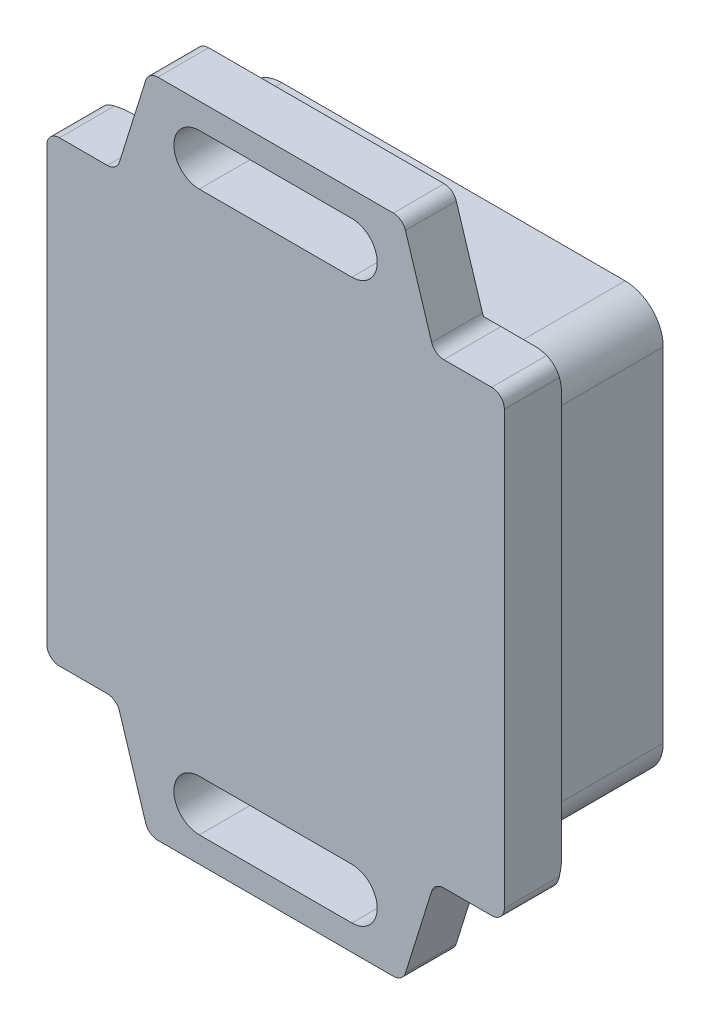
SolidWorks part; units mm, degrees
ref_plane "Plan de face" through (0, 0, 0) normal (0, 0, 1) x (1, 0, 0)
ref_plane "Plan de dessus" through (0, 0, 0) normal (0, 1, 0) x (1, 0, 0)
ref_plane "Plan de droite" through (0, 0, 0) normal (1, 0, 0) x (0, 0, -1)
sketch "Esquisse1" plane through (0, 0, 0) normal (0, 0, 1) x (1, 0, 0)
  line L1 (10.5, 10.5) -> (-10.5, 10.5)
  line L2 (10.5, 10.5) -> (10.5, -10.5)
  line L3 (10.5, -10.5) -> (-10.5, -10.5)
  line L4 (-10.5, 10.5) -> (-10.5, -10.5)
  line L5 (10.5, 10.5) -> (-10.5, -10.5) construction
  line L6 (10.5, -10.5) -> (-10.5, 10.5) construction
  line L7 (16.5, 16.5) -> (-16.5, 16.5)
  line L8 (16.5, 16.5) -> (16.5, -16.5)
  line L9 (16.5, -16.5) -> (-16.5, -16.5)
  line L10 (-16.5, 16.5) -> (-16.5, -16.5)
  line L11 (16.5, 16.5) -> (-16.5, -16.5) construction
  line L12 (16.5, -16.5) -> (-16.5, 16.5) construction
  point P0 (0, 0)
  point P6 (0, 0)
  dimension "D1" = 21
  dimension "D2" = 6
  dimension "D3" = 6
extrude "Boss.-Extru.1" add sketch "Esquisse1" along normal blind 10
sketch "Esquisse2" plane through (0, 0, 10) normal (0, 0, 1) x (1, 0, 0)
  line L2 (18, 18) -> (-18, 18)
  line L3 (18, 18) -> (18, -18)
  line L4 (18, -18) -> (-18, -18)
  line L5 (-10.5, 10.5) -> (-10.5, -10.5)
  line L6 (10.5, 10.5) -> (-10.5, 10.5)
  line L7 (10.5, -10.5) -> (10.5, 10.5)
  line L8 (-10.5, -10.5) -> (10.5, -10.5)
  line L9 (-10.5, 10.5) -> (-10.5, -10.5)
  line L10 (10.5, 10.5) -> (-10.5, 10.5)
  line L11 (10.5, -10.5) -> (10.5, 10.5)
  line L12 (-10.5, -10.5) -> (10.5, -10.5)
  line L13 (-18, 18) -> (-18, -18)
  line L14 (18, 18) -> (-18, -18) construction
  line L15 (18, -18) -> (-18, 18) construction
  point P0 (0, 0)
  dimension "D2" = 36
  dimension "D3" = 36
  dimension "D1" = 0
extrude "Boss.-Extru.2" add sketch "Esquisse2" along normal blind 4
sketch "Esquisse3" plane through (0, 0, 14) normal (0, 0, 1) x (1, 0, 0)
  line L0 (0, 0) -> (18, 0) construction
  line L1 (18, -18) -> (18, 18) construction
  line L2 (0, 18) -> (0, 0) construction
  line L3 (18, 18) -> (-18, 18) construction
  line L4 (12.5, 18) -> (-12.5, 18)
  line L5 (-12.5, 18) -> (-10, 26)
  line L6 (-10, 26) -> (10, 26)
  line L7 (0, 18) -> (0, 26) construction
  line L8 (12.5, 18) -> (10, 26)
  line L9 (0, -18) -> (0, -26) construction
  line L10 (12.5, -18) -> (10, -26)
  line L11 (-10, -26) -> (10, -26)
  line L12 (-12.5, -18) -> (-10, -26)
  line L13 (12.5, -18) -> (-12.5, -18)
  line L14 (-6, 22) -> (6, 22) construction
  line L15 (-6, 24) -> (6, 24)
  line L16 (-6, 20) -> (6, 20)
  line L17 (-6, -22) -> (6, -22) construction
  line L18 (-6, -24) -> (6, -24)
  line L19 (-6, -20) -> (6, -20)
  arc A0 (-6, 24) -> (-6, 20) centre (-6, 22) ccw
  arc A1 (6, 20) -> (6, 24) centre (6, 22) ccw
  arc A2 (-6, -24) -> (-6, -20) centre (-6, -22) cw
  arc A3 (6, -20) -> (6, -24) centre (6, -22) cw
  point P21 (0, 22)
  point P28 (0, -22)
  dimension "D1" = 8
  dimension "D2" = 25
  dimension "D3" = 20
  dimension "D4" = 4
  dimension "D5" = 12
extrude "Boss.-Extru.3" add sketch "Esquisse3" against normal blind 4
chamfer "Chanfrein1" distance 2 angle 45 4 edges at (0, -16.5, 10) (16.5, 0, 10) (0, 16.5, 10) (-16.5, 0, 10)
fillet "Congé1" radius 1 16 edges at (18, -18, 11.75) (12.5, -18, 11.75) (10, -26, 12) (-10, -26, 12) (-12.5, -18, 11.75) (-18, -18, 11.75) (-12.5, 18, 11.75) (-18, 18, 11.75) (18, 18, 11.75) (12.5, 18, 11.75) (-10, 26, 12) (10, 26, 12) (10.5, -10.5, 7) (10.5, 10.5, 7) (-10.5, 10.5, 7) (-10.5, -10.5, 7)
fillet "Congé2" radius 3 8 edges at (17.1036, -17.1036, 8.6036) (-17.1036, -17.1036, 8.6036) (-17.1036, 17.1036, 8.6036) (17.1036, 17.1036, 8.6036) (16.5, 16.5, 4) (16.5, -16.5, 4) (-16.5, 16.5, 4) (-16.5, -16.5, 4)
sketch "Esquisse4" plane through (0, 0, 14) normal (0, 0, 1) x (1, 0, 0)
  line L5 (-9.5, -10.5) -> (9.5, -10.5)
  line L6 (-10.5, 9.5) -> (-10.5, -9.5)
  line L7 (9.5, 10.5) -> (-9.5, 10.5)
  line L8 (10.5, -9.5) -> (10.5, 9.5)
  line L9 (-9.5, -10.5) -> (9.5, -10.5)
  line L10 (-10.5, 9.5) -> (-10.5, -9.5)
  line L11 (9.5, 10.5) -> (-9.5, 10.5)
  line L12 (10.5, -9.5) -> (10.5, 9.5)
  arc A4 (-10.5, -9.5) -> (-9.5, -10.5) centre (-9.5, -9.5) ccw
  arc A5 (-9.5, 10.5) -> (-10.5, 9.5) centre (-9.5, 9.5) ccw
  arc A6 (10.5, 9.5) -> (9.5, 10.5) centre (9.5, 9.5) ccw
  arc A7 (9.5, -10.5) -> (10.5, -9.5) centre (9.5, -9.5) ccw
  arc A8 (-10.5, -9.5) -> (-9.5, -10.5) centre (-9.5, -9.5) ccw
  arc A9 (-9.5, 10.5) -> (-10.5, 9.5) centre (-9.5, 9.5) ccw
  arc A10 (10.5, 9.5) -> (9.5, 10.5) centre (9.5, 9.5) ccw
  arc A11 (9.5, -10.5) -> (10.5, -9.5) centre (9.5, -9.5) ccw
  dimension "D1" = 0
extrude "Boss.-Extru.4" add sketch "Esquisse4" against normal blind 1
chamfer "Chanfrein2" distance 1 angle 45 8 edges at (0, -10.5, 0) (10.2071, -10.2071, 0) (-10.2071, -10.2071, 0) (10.5, 0, 0) (-10.5, 0, 0) (10.2071, 10.2071, 0) (-10.2071, 10.2071, 0) (0, 10.5, 0)
